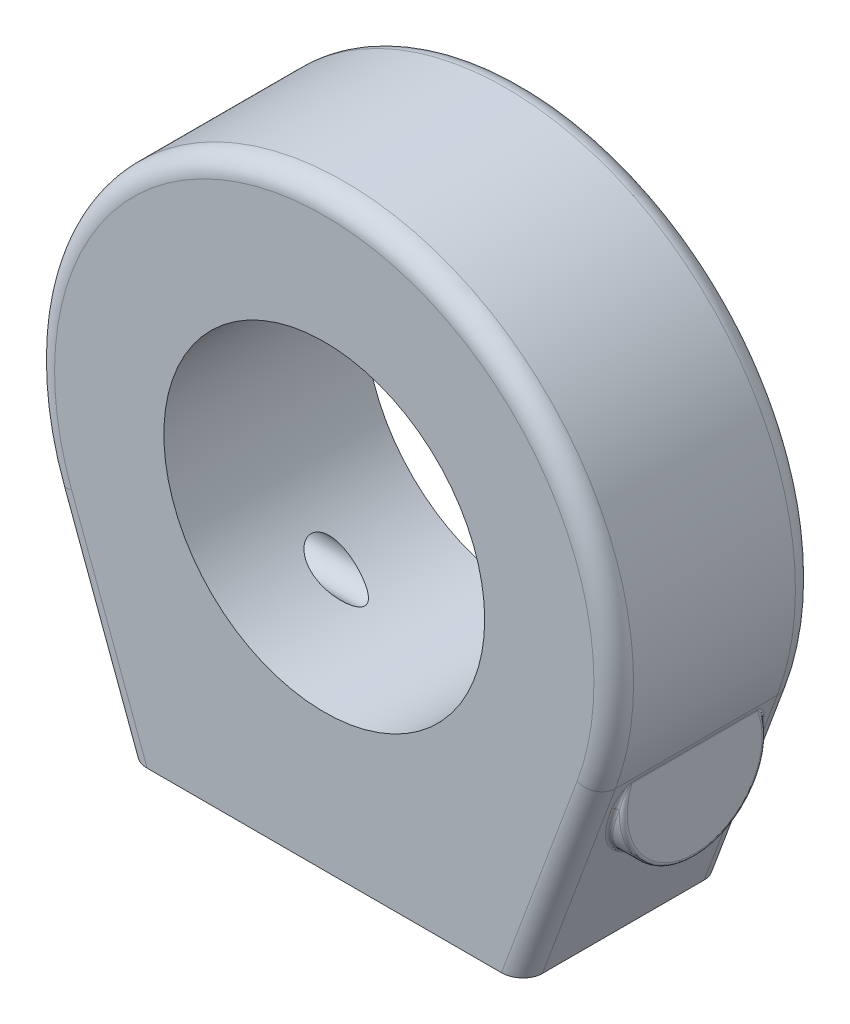
SolidWorks part; units mm, degrees
ref_plane "Płaszczyzna przednia" through (0, 0, 0) normal (0, 0, 1) x (1, 0, 0)
ref_plane "Płaszczyzna górna" through (0, 0, 0) normal (0, 1, 0) x (1, 0, 0)
ref_plane "Płaszczyzna prawa" through (0, 0, 0) normal (1, 0, 0) x (0, 0, -1)
sketch "Szkic1" plane through (0, 0, 0) normal (0, 0, 1) x (1, 0, 0)
  line L0 (-50, -75) -> (50, -75)
  line L1 (0, 0) -> (0, -75) construction
  line L2 (-50, -75) -> (-68.425, -25.4367)
  line L3 (50, -75) -> (68.425, -25.4367)
  circle A0 centre (0, 0) radius 73
  circle A1 centre (0, 0) radius 40.45
  dimension "D1" = 146
  dimension "D4" = 80.9
  dimension "D2" = 100
  dimension "D3" = 75
extrude "Dodanie-wyciągnięcie1" add sketch "Szkic1" along normal blind 50.8 contours A0 | L1 A0 L2 L0 | A0 L1 L0 L3 region at (-40.4059, -64.8267, 0) region at (40.4059, -64.8267, 0) region at (-12.5569, 69.815, 0)
fillet "Zaokrąglenie1" radius 5 6 edges at (59.2125, -50.2183, 0) (-59.2125, -50.2183, 0) (59.2125, -50.2183, 50.8) (-59.2125, -50.2183, 50.8) (0, 73, 0) (0, 73, 50.8)
ref_plane "Płaszczyzna1" through (-68, 0, 0) normal (1, 0, 0) x (0, 0, -1)
sketch "Szkic2" plane through (-68, 0, 0) normal (1, 0, 0) x (0, 0, -1)
  circle A0 centre (-25.4, -33) radius 18
  dimension "D2" = 36
  dimension "D1" = 33
  dimension "D3" = 25.4
extrude "Dodanie-wyciągnięcie2" add sketch "Szkic2" along normal up to next
fillet "Zaokrąglenie2" radius 1 3 edges at (-68, -26.5798, 25.4) (-58.9219, -51, 25.4) (-68, -51, 25.4)
mirror "Lustro1" about plane through (0, 0, 0) normal (1, 0, 0) of "Dodanie-wyciągnięcie2", "Zaokrąglenie2"
sketch "Szkic3" plane through (-68, 0, 0) normal (-1, 0, 0) x (0, 0, 1)
  circle A0 centre (25.4, -33) radius 10.5
  dimension "D1" = 21
extrude "Wytnij-wyciągnięcie1" cut sketch "Szkic3" against normal blind 14
sketch "Szkic4" plane through (-54, 0, 0) normal (-1, 0, 0) x (0, 0, 1)
  circle A0 centre (25.4, -33) radius 4.5
  dimension "D1" = 9
extrude "Wytnij-wyciągnięcie2" cut sketch "Szkic4" against normal blind 44
